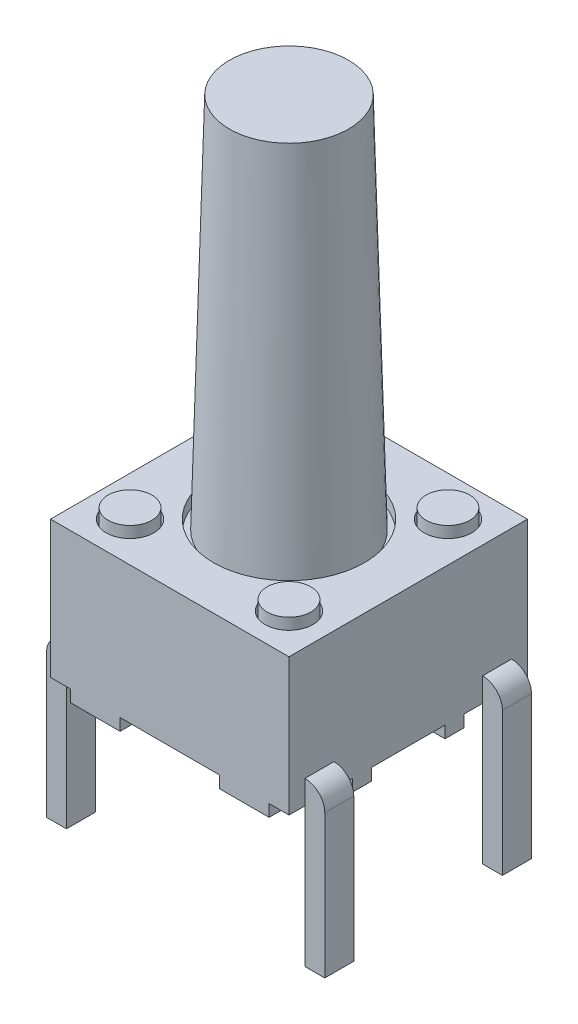
SolidWorks part; units mm, degrees
ref_plane "Front Plane" through (0, 0, 0) normal (0, 0, 1) x (1, 0, 0)
ref_plane "Top Plane" through (0, 0, 0) normal (0, 1, 0) x (1, 0, 0)
ref_plane "Right Plane" through (0, 0, 0) normal (1, 0, 0) x (0, 0, -1)
sketch "Sketch1" plane through (0, 0, 0) normal (0, 1, 0) x (1, 0, 0)
  line L1 (-3, 3) -> (3, 3)
  line L2 (-3, 3) -> (-3, -3)
  line L3 (-3, -3) -> (3, -3)
  line L4 (3, 3) -> (3, -3)
  dimension "D1" = 6
  dimension "D2" = 6
  dimension "D3" = 3
  dimension "D4" = 3
extrude "Boss-Extrude1" add sketch "Sketch1" along normal blind 3.45
sketch "Sketch2" plane through (0, 3.45, 0) normal (0, 1, 0) x (1, 0, 0)
  line L4 (-3, 3) -> (-3, -3)
  line L5 (-3, -3) -> (3, -3)
  line L6 (3, -3) -> (3, 3)
  line L7 (3, 3) -> (-3, 3)
  line L8 (-3, 3) -> (-3, -3)
  line L9 (-3, -3) -> (3, -3)
  line L10 (3, -3) -> (3, 3)
  line L11 (3, 3) -> (-3, 3)
  circle A0 centre (-2, 2) radius 0.6
  circle A1 centre (2, 2) radius 0.6
  circle A2 centre (2, -2) radius 0.6
  circle A3 centre (-2, -2) radius 0.6
  circle A4 centre (0, 0) radius 1.9
  dimension "D2" = 1.2
  dimension "D7" = 3.8
  dimension "D3" = 1
  dimension "D4" = 1
  dimension "D5" = 1
  dimension "D6" = 1
  dimension "D8" = 3
  dimension "D9" = 3
  dimension "D1" = 0
extrude "Boss-Extrude2" add sketch "Sketch2" along normal blind 0.3 separate body
sketch "Sketch3" plane through (0, 3.45, 0) normal (0, 1, 0) x (1, 0, 0)
  circle A16 centre (-2, 2) radius 0.55
  circle A17 centre (-2, -2) radius 0.55
  circle A18 centre (2, 2) radius 0.55
  circle A19 centre (2, -2) radius 0.55
  dimension "D1" = 1.1
extrude "Boss-Extrude3" add sketch "Sketch3" along normal offset from surface (0.55 mm away) 4 up to face at (0, 0, 0)
sketch "Sketch4" plane through (0, 0, 0) normal (0, 0, 1) x (1, 0, 0)
  line L0 (0, 0) -> (0, 13) construction
  line L1 (-3, 0) -> (3, 0) construction
  line L2 (0, 13) -> (-1.5, 13)
  line L3 (-1.5, 13) -> (-1.75, 3.5061)
  line L4 (-1.75, 3.5061) -> (0, 3.5061)
  line L5 (0, 3.5061) -> (0, 13)
  dimension "D1" = 1.75
  dimension "D2" = 1.5
  dimension "D3" = 13
revolve "Revolve1" add sketch "Sketch4" angle 360 about L0
sketch "Sketch5" plane through (0, 0, 0) normal (0, -1, 0) x (1, 0, 0)
  line L0 (-3, 3) -> (3, 3) construction
  line L1 (-1.25, 3) -> (1.25, 3)
  line L2 (-1.25, 3) -> (-1.25, 1.4)
  line L3 (-1.25, 1.4) -> (1.25, 1.4)
  line L4 (1.25, 3) -> (1.25, 1.4)
  line L5 (-3, 0) -> (3, 0) construction
  line L6 (-3, -3) -> (-3, 3) construction
  line L7 (3, 3) -> (3, -3) construction
  line L8 (0, 3) -> (0, -3) construction
  line L9 (3, -3) -> (-3, -3) construction
  line L10 (-3, -0.925) -> (3, -0.925)
  line L11 (-3, 3) -> (-2.5, 3)
  line L12 (-3, 3) -> (-3, 1.4)
  line L13 (-3, 1.4) -> (-2.5, 1.4)
  line L14 (-2.5, 3) -> (-2.5, 1.4)
  line L15 (3, 3) -> (2.5, 3)
  line L16 (3, 3) -> (3, 1.4)
  line L17 (3, 1.4) -> (2.5, 1.4)
  line L18 (2.5, 3) -> (2.5, 1.4)
  line L19 (2.5, -3) -> (2.5, -1.4)
  line L20 (-3, -0.925) -> (-3, 0.925)
  line L21 (-3, 0.925) -> (3, 0.925)
  line L22 (3, -0.925) -> (3, 0.925)
  line L23 (3, -1.4) -> (2.5, -1.4)
  line L24 (3, -3) -> (3, -1.4)
  line L25 (3, -3) -> (2.5, -3)
  line L26 (-2.5, -3) -> (-2.5, -1.4)
  line L27 (-3, -1.4) -> (-2.5, -1.4)
  line L28 (-3, -3) -> (-3, -1.4)
  line L29 (-3, -3) -> (-2.5, -3)
  line L30 (1.25, -3) -> (1.25, -1.4)
  line L31 (-1.25, -1.4) -> (1.25, -1.4)
  line L32 (-1.25, -3) -> (-1.25, -1.4)
  line L33 (-1.25, -3) -> (1.25, -3)
  dimension "D1" = 2.5
  dimension "D2" = 1.25
  dimension "D3" = 0.5
  dimension "D4" = 1.4
  dimension "D5" = 0.5
  dimension "D6" = 0.925
extrude "Cut-Extrude1" cut sketch "Sketch5" against normal blind 0.3
sketch "Sketch6" plane through (0, 0.3, 0) normal (0, -1, 0) x (1, 0, 0)
  line L0 (-3, 3) -> (-3, 1.4) construction
  line L1 (-3, 2.6) -> (-3.5, 2.6)
  line L2 (-3, 2.6) -> (-3, 1.87)
  line L3 (-3, 1.87) -> (-3.5, 1.87)
  line L4 (-3.5, 2.6) -> (-3.5, 1.87)
  line L6 (-2.5, 3) -> (-3, 3) construction
  line L7 (0, 3) -> (0, -3) construction
  line L8 (1.25, 3) -> (-1.25, 3) construction
  line L9 (-1.25, -3) -> (1.25, -3) construction
  line L10 (-3, 0) -> (3, 0) construction
  line L11 (-3, 0.925) -> (-3, -0.925) construction
  line L12 (3, -0.925) -> (3, 0.925) construction
  line L13 (3, 2.6) -> (3, 1.87)
  line L14 (3, 2.6) -> (3.5, 2.6)
  line L15 (3.5, 2.6) -> (3.5, 1.87)
  line L16 (3, 1.87) -> (3.5, 1.87)
  line L17 (3, -1.87) -> (3.5, -1.87)
  line L18 (3.5, -2.6) -> (3.5, -1.87)
  line L19 (3, -2.6) -> (3.5, -2.6)
  line L20 (3, -2.6) -> (3, -1.87)
  line L21 (-3.5, -2.6) -> (-3.5, -1.87)
  line L22 (-3, -1.87) -> (-3.5, -1.87)
  line L23 (-3, -2.6) -> (-3, -1.87)
  line L24 (-3, -2.6) -> (-3.5, -2.6)
  dimension "D1" = 0.5
  dimension "D2" = 0.73
  dimension "D3" = 0.4
extrude "Boss-Extrude4" add sketch "Sketch6" along normal blind 3.5 and the other way blind 0.6 separate body
fillet "Fillet1" radius 0.5 1 edges at (-3.5, 0.9, 2.235) tangent propagation no
fillet "Fillet2" radius 0.5 1 edges at (-3.5, 0.9, -2.235)
fillet "Fillet3" radius 0.5 1 edges at (3.5, 0.9, 2.235)
fillet "Fillet4" radius 0.5 1 edges at (3.5, 0.9, -2.235)
